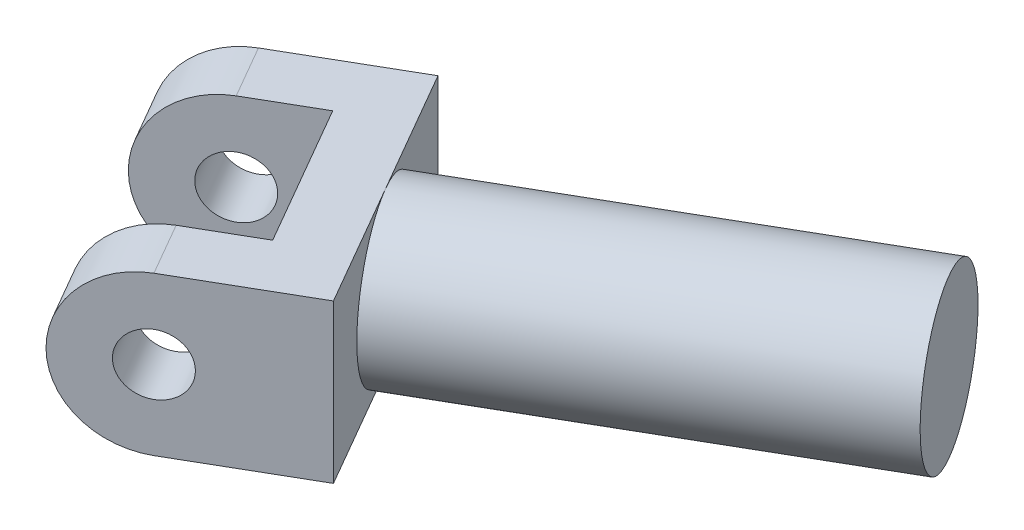
SolidWorks part; units mm, degrees
material "1060 Alloy"
ref_plane "Front Plane" through (0, 0, 0) normal (0, 0, 1) x (1, 0, 0)
ref_plane "Top Plane" through (0, 0, 0) normal (0, 1, 0) x (1, 0, 0)
ref_plane "Right Plane" through (0, 0, 0) normal (1, 0, 0) x (0, 0, -1)
sketch "Sketch1" plane through (0, 0, 0) normal (0, 1, 0) x (1, 0, 0)
  line L0 (86.6025, 150) -> (0, 0) construction
  line L1 (173.2051, 0) -> (0, 0) construction
  line L2 (86.6025, 150) -> (103.923, 160)
  line L3 (158.0737, 16.2083) -> (93.0737, 128.7917)
  line L4 (181.5544, 35.5385) -> (194.8557, 12.5) construction
  line L5 (173.2051, 0) -> (194.8557, 12.5) construction
  line L6 (86.6025, -150) -> (173.2051, 0) construction
  line L7 (173.2051, 0) -> (159.9038, 23.0385) construction
  line L8 (159.9038, 23.0385) -> (181.5544, 35.5385) construction
  line L9 (181.5544, 35.5385) -> (121.5544, 139.4615) construction
  line L10 (121.5544, 139.4615) -> (99.9038, 126.9615) construction
  line L12 (86.6025, 150) -> (-86.6025, 150) construction
  line L13 (-86.6025, 150) -> (-99.9038, 126.9615) construction
  line L14 (-99.9038, 126.9615) -> (-121.5544, 139.4615) construction
  line L15 (-121.5544, 139.4615) -> (-181.5544, 35.5385) construction
  line L16 (-181.5544, 35.5385) -> (-159.9038, 23.0385) construction
  line L17 (-159.9038, 23.0385) -> (-173.2051, 0) construction
  line L18 (-173.2051, 0) -> (-86.6025, -150) construction
  line L19 (-86.6025, -150) -> (-60, -150) construction
  line L20 (-60, -150) -> (-60, -175) construction
  line L21 (-60, -175) -> (60, -175) construction
  line L22 (60, -175) -> (60, -150) construction
  line L23 (60, -150) -> (86.6025, -150) construction
  line L24 (22.799, 39.489) -> (45.598, 0)
  line L25 (22.799, 39.489) -> (86.6025, 150)
  line L26 (151.5544, 87.5) -> (34.1985, 19.7445) construction
  line L27 (114.7243, 141.2917) -> (103.923, 160)
  line L28 (114.7243, 141.2917) -> (93.0737, 128.7917)
  line L29 (45.598, 0) -> (173.2051, 0)
  line L30 (173.2051, 0) -> (190.5256, 10)
  line L31 (179.7243, 28.7083) -> (190.5256, 10)
  line L32 (179.7243, 28.7083) -> (158.0737, 16.2083)
  line L33 (0, 0) -> (131.7313, -228.1653) construction
  line L34 (140.7291, 81.25) -> (272.4604, -146.9153) construction
  point P4 (101.6025, 168.75)
  point P22 (88.923, 130.7115)
  point P26 (75.6218, 153.75)
  point P34 (125.5737, 72.5)
  dimension "D1" = 162.5
extrude "Boss-Extrude1" add sketch "Sketch1" along normal mid plane 50
ref_plane "Plane1" through (140.7291, 0, -81.25) normal (0.5, 0, 0.866) x (0.866, 0, -0.5)
sketch "Sketch2" plane through (140.7291, 0, -81.25) normal (0.5, 0, 0.866) x (0.866, 0, -0.5)
  line L0 (0, 0) -> (0, -100.0987) construction
  line L1 (12.5, 0) -> (-12.5, 0) construction
  circle A0 centre (0, 0) radius 8
extrude "Cut-Extrude1" cut sketch "Sketch2" against normal mid plane 220
sketch "Sketch3" plane through (140.7291, 0, -81.25) normal (0.5, 0, 0.866) x (0.866, 0, -0.5)
  line L0 (0, 18) -> (-12.5, 18)
  line L1 (-12.5, 25) -> (-12.5, -25) construction
  line L2 (0, -18) -> (-12.5, -18)
  line L3 (-12.5, 18) -> (-12.5, 31.3122)
  line L4 (-12.5, 31.3122) -> (23.9059, 31.3122)
  line L5 (23.9059, 31.3122) -> (23.9059, -29.5052)
  line L6 (-12.5, -29.5052) -> (23.9059, -29.5052)
  line L7 (-12.5, -18) -> (-12.5, -29.5052)
  arc A0 (0, -18) -> (0, 18) centre (0, 0) ccw
extrude "Cut-Extrude2" cut sketch "Sketch3" against normal mid plane 300
ref_plane "Plane2" through (173.2291, 0, -24.9583) normal (0.5, 0, 0.866) x (0.866, 0, -0.5)
sketch "Sketch4" plane through (173.2291, 0, -24.9583) normal (0.5, 0, 0.866) x (0.866, 0, -0.5)
  line L2 (7.5, 16.3631) -> (7.5, 2.7839)
  line L3 (7.5, -2.7839) -> (7.5, -16.3631)
  line L7 (-12.5, 18) -> (0, 18)
  line L8 (-12.5, 31.3122) -> (-12.5, 18)
  line L9 (23.9059, 31.3122) -> (-12.5, 31.3122)
  line L10 (23.9059, -29.5052) -> (23.9059, 31.3122)
  line L11 (-12.5, -29.5052) -> (23.9059, -29.5052)
  line L12 (-12.5, -18) -> (-12.5, -29.5052)
  line L13 (0, -18) -> (-12.5, -18)
  arc A0 (7.5, -2.7839) -> (7.5, 2.7839) centre (0, 0) ccw
  arc A1 (0, -18) -> (0, 18) centre (0, 0) ccw
  arc A2 (7.5, -16.3631) -> (7.5, 16.3631) centre (0, 0) ccw
  dimension "D1" = 0
extrude "Boss-Extrude2" add sketch "Sketch4" along normal blind 21.6025
mirror "Mirror2" about plane through (140.7291, 0, -81.25) normal (0.5, 0, 0.866) of "Boss-Extrude2"
sketch "Sketch5" plane through (34.1985, 0, -19.7445) normal (-0.866, 0, 0.5) x (0.5, 0, 0.866)
  circle A0 centre (0, 0) radius 13
extrude "Cut-Extrude3" cut sketch "Sketch5" against normal blind 50
sketch "Sketch6" plane through (77.4998, 0, -44.7445) normal (-0.866, 0, 0.5) x (0.5, 0, 0.866)
  circle A1 centre (0, 0) radius 13
  circle A2 centre (0, 0) radius 13
  dimension "D1" = 0
extrude "Boss-Extrude3" add sketch "Sketch6" along normal blind 100 separate body
sketch "Sketch7" plane through (140.7291, 0, -81.25) normal (0.5, 0, 0.866) x (0.866, 0, -0.5)
  circle A0 centre (-162.5, 0) radius 5
extrude "Cut-Extrude4" cut sketch "Sketch7" against normal mid plane 100
sketch "Sketch8" plane through (140.7291, 0, -81.25) normal (0.5, 0, 0.866) x (0.866, 0, -0.5)
  circle A0 centre (-162.5, 0) radius 13
  circle A1 centre (-162.5, 0) radius 5
extrude "Boss-Extrude4" add sketch "Sketch8" along normal mid plane 26
sketch "Sketch9" plane through (140.7291, 0, -81.25) normal (0.5, 0, 0.866) x (0.866, 0, -0.5)
  line L0 (-162.5, 18.8341) -> (-162.5, 13)
  line L1 (-162.5, -13) -> (-162.5, -19.8118)
  arc A0 (-162.5, 13) -> (-162.5, -13) centre (-162.5, 0) ccw
  arc A1 (-162.5, 18.8341) -> (-162.5, -18.8341) centre (-162.5, 0) ccw
extrude "Cut-Extrude5" cut sketch "Sketch9" against normal mid plane 56 contours L0 A1 L1 A0 region at (-0.3647, 15.917, 0.2106)
delete or keep bodies "Body-Delete/Keep 1" type delete bodies bodies 106
ref_plane "Plane3" through (0, 0, 0) normal (0.5, 0, 0.866) x (0.866, 0, -0.5)
ref_axis "Axis1" through (-8.6651, 0, -15.0083) along (0.5, 0, 0.866)
ref_axis "Axis2" through (24.2499, 0, -14.0007) along (0.866, 0, -0.5)
ref_plane "Plane4" through (6.75, 0, 11.6913) normal (0.5, 0, 0.866) x (0.866, 0, -0.5)
sketch "Sketch10" plane through (6.75, 0, 11.6913) normal (0.5, 0, 0.866) x (0.866, 0, -0.5)
  line L0 (0, 13) -> (21.6263, 13)
  line L1 (89.489, 13) -> (0, 13) construction
  line L2 (21.6263, 13) -> (21.6263, -13)
  line L3 (0, -13) -> (21.6263, -13)
  circle A0 centre (0, 0) radius 5 construction
  circle A1 centre (0, 0) radius 13
  arc A2 (0, 13) -> (0, -13) centre (0, 0) ccw
  circle A3 centre (0, 0) radius 5
  dimension "D1" = 0
extrude "Boss-Extrude5" add sketch "Sketch10" along normal blind 10 separate body
pattern_circular "CirPattern2" count 2 over 360 about axis through (24.2499, 0, -14.0007) along (0.866, 0, -0.5) of bodies 111
sketch "Sketch11" plane through (18.7289, 0, -10.8131) normal (0.866, 0, -0.5) x (-0.5, 0, -0.866)
  line L1 (-23.5, 13) -> (23.5, 13)
  line L2 (-23.5, 13) -> (-23.5, -13)
  line L3 (-23.5, -13) -> (23.5, -13)
  line L4 (23.5, 13) -> (23.5, -13)
extrude "Boss-Extrude6" add sketch "Sketch11" against normal blind 10 separate body
sketch "Sketch12" plane through (18.7289, 0, -10.8131) normal (0.866, 0, -0.5) x (-0.5, 0, -0.866)
  circle A0 centre (0, 0) radius 13 construction
  circle A1 centre (0, 0) radius 13
extrude "Boss-Extrude7" add sketch "Sketch12" along normal blind 67.8628 separate body
combine bodies "Combine2" operation type add bodies to combine 112 113 114 111
delete or keep bodies "Body-Delete/Keep 2" type delete bodies bodies 110
ref_plane "Plane5" through (0, 0, 0) normal (0, -1, 0) x (0.866, 0, -0.5)
scale "Scale1" scale about origin uniform scaling yes scale factor 3.5
